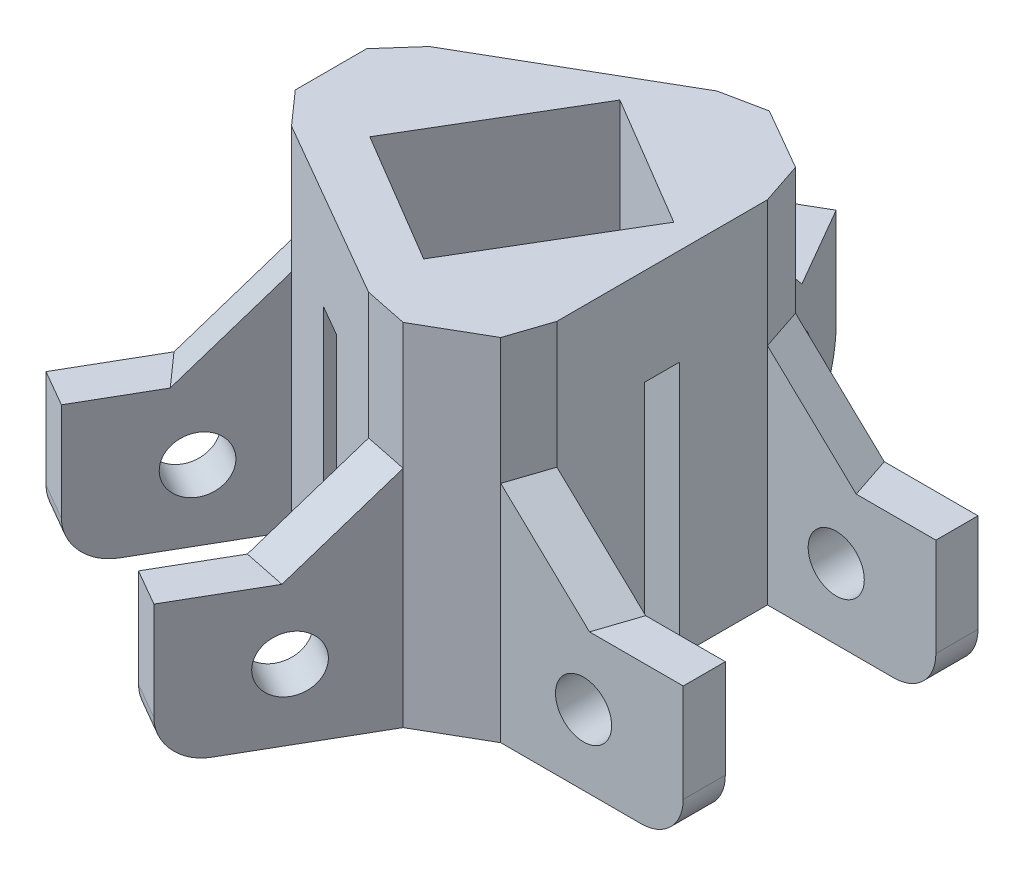
SolidWorks part; units mm, degrees
ref_plane "Front Plane" through (0, 0, 0) normal (0, 0, 1) x (1, 0, 0)
ref_plane "Top Plane" through (0, 0, 0) normal (0, 1, 0) x (1, 0, 0)
ref_plane "Right Plane" through (0, 0, 0) normal (1, 0, 0) x (0, 0, -1)
sketch "Sketch1" plane through (0, 0, 0) normal (0, 1, 0) x (1, 0, 0)
  line L13 (10, 7.5) -> (10, -7.5)
  line L24 (10, 7.5) -> (22, 7.5)
  line L62 (22, 7.5) -> (22, 10.5)
  line L64 (10, -7.5) -> (22, -7.5)
  line L66 (22, -7.5) -> (22, -10.5)
  line L67 (9, -10.5) -> (22, -10.5)
  line L68 (1.4952, -12.4103) -> (-4.5048, -22.8026)
  line L71 (-4.5048, -22.8026) -> (-1.9067, -24.3026)
  line L72 (-11.4952, -4.9103) -> (-17.4952, -15.3026)
  line L74 (-13.5933, -2.5442) -> (-20.0933, -13.8026)
  line L75 (-17.4952, -15.3026) -> (-20.0933, -13.8026)
  line L76 (-11.4952, 4.9103) -> (-17.4952, 15.3026)
  line L79 (-17.4952, 15.3026) -> (-20.0933, 13.8026)
  line L80 (1.4952, 12.4103) -> (-4.5048, 22.8026)
  line L82 (4.5933, 13.0442) -> (-1.9067, 24.3026)
  line L83 (-4.5048, 22.8026) -> (-1.9067, 24.3026)
  line L84 (1.4952, -12.4103) -> (-11.4952, -4.9103)
  line L85 (-11.4952, 4.9103) -> (1.4952, 12.4103)
  line L86 (22, 10.5) -> (9, 10.5)
  line L87 (-1.9067, -24.3026) -> (4.5933, -13.0442)
  line L88 (-20.0933, 13.8026) -> (-13.5933, 2.5442)
  line L89 (9, 10.5) -> (4.5933, 13.0442)
  line L90 (-13.5933, 2.5442) -> (-13.5933, -2.5442)
  line L91 (4.5933, -13.0442) -> (9, -10.5)
  circle A0 centre (0, 0) radius 3.5
  circle A13 centre (0, 0) radius 25 construction
  point P5 (10, 0)
  point P19 (0, 0)
  point P36 (0, 0)
  point P56 (0, 0)
  dimension "D1" = 7
  dimension "D9" = 13
  dimension "D10" = 10
  dimension "D6" = 12
  dimension "D2" = 15
  dimension "D3" = 3
  dimension "D5" = 3
  dimension "D7" = 3
  dimension "D8" = 13
  dimension "D4" = 12
extrude "Boss-Extrude1" add sketch "Sketch1" along normal mid plane 10
sketch "Sketch2" plane through (6.0622, 0, 0) normal (0, 0, 1) x (1, 0, 0)
  line L6 (-6.0622, -5) -> (-6.0622, 5) construction
  circle A0 centre (8.8378, 0) radius 3 construction
  circle A1 centre (8.8378, 0) radius 2
  dimension "D1" = 4
  dimension "D2" = 6
  dimension "D3" = 14.9
extrude "Cut-Extrude1" cut sketch "Sketch2" against normal mid plane 25 contours A1 region at (14.9, 0, 0)
sketch "Sketch5" plane through (0, 5, 0) normal (0, 1, 0) x (1, 0, 0)
  line L0 (-1.4081, 8.3975) -> (8.0486, 2.7786) construction
  line L5 (-1.4081, 8.3975) -> (8.0486, 2.7786)
  line L6 (-1.4081, 8.3975) -> (-8.0486, -2.7786)
  line L7 (8.0486, 2.7786) -> (1.4081, -8.3975)
  line L8 (-8.0486, -2.7786) -> (1.4081, -8.3975)
  line L9 (-1.4081, 8.3975) -> (1.4081, -8.3975) construction
  line L10 (-11.4952, 4.9103) -> (-13.5933, 2.5442)
  line L11 (-13.5933, -2.5442) -> (-11.4952, -4.9103)
  line L12 (1.4952, -12.4103) -> (4.5933, -13.0442)
  line L13 (9, -10.5) -> (10, -7.5)
  line L14 (10, 7.5) -> (9, 10.5)
  line L15 (4.5933, 13.0442) -> (1.4952, 12.4103)
  line L20 (22, -10.5) -> (22, -7.5)
  line L34 (-13.5933, -2.5442) -> (-20.0933, -13.8026)
  line L35 (-20.0933, -13.8026) -> (-17.4952, -15.3026)
  line L36 (-17.4952, -15.3026) -> (-11.4952, -4.9103)
  line L73 (22, -7.5) -> (10, -7.5)
  line L75 (10, -7.5) -> (10, 7.5)
  line L77 (10, -7.5) -> (10, 7.5)
  line L79 (10, 7.5) -> (22, 7.5)
  line L81 (22, 7.5) -> (22, 10.5)
  line L83 (4.5933, 13.0442) -> (-1.9067, 24.3026)
  line L85 (-1.9067, 24.3026) -> (-4.5048, 22.8026)
  line L87 (-4.5048, 22.8026) -> (1.4952, 12.4103)
  line L88 (1.4952, 12.4103) -> (-11.4952, 4.9103)
  line L89 (1.4952, 12.4103) -> (-11.4952, 4.9103)
  line L91 (-11.4952, 4.9103) -> (-17.4952, 15.3026)
  line L92 (-17.4952, 15.3026) -> (-20.0933, 13.8026)
  line L93 (-11.4952, -4.9103) -> (1.4952, -12.4103)
  line L94 (-11.4952, -4.9103) -> (1.4952, -12.4103)
  line L95 (1.4952, -12.4103) -> (-4.5048, -22.8026)
  line L97 (-4.5048, -22.8026) -> (-1.9067, -24.3026)
  line L98 (9, -10.5) -> (22, -10.5)
  line L100 (22, 10.5) -> (9, 10.5)
  line L101 (9, 10.5) -> (4.5933, 13.0442)
  line L103 (9, 10.5) -> (4.5933, 13.0442)
  line L104 (-20.0933, 13.8026) -> (-13.5933, 2.5442)
  line L105 (-13.5933, 2.5442) -> (-13.5933, -2.5442)
  line L106 (-13.5933, 2.5442) -> (-13.5933, -2.5442)
  line L107 (-1.9067, -24.3026) -> (4.5933, -13.0442)
  line L108 (4.5933, -13.0442) -> (9, -10.5)
  line L109 (4.5933, -13.0442) -> (9, -10.5)
  point P2 (0, 0)
  point P8 (0, 0)
  dimension "D2" = 11
  dimension "D3" = 13
  dimension "D1" = 0
extrude "Boss-Extrude2" add sketch "Sketch5" along normal blind 15
chamfer "Chamfer1" distance 6 angle 45 6 edges at (3.0442, 5, -12.7272) (-12.5442, 5, -3.7272) (-12.5442, 5, 3.7272) (3.0442, 5, 12.7272) (9.5, 5, 9) (9.5, 5, -9)
fillet "Fillet1" radius 3 6 edges at (-3.2058, -5, -23.5526) (22, -5, -9) (22, -5, 9) (-3.2058, -5, 23.5526) (-18.7942, -5, 14.5526) (-18.7942, -5, -14.5526)
sketch "Sketch6" plane through (0, 0, 0) normal (0, 0, 1) x (1, 0, 0)
  circle A0 centre (14.9, 0) radius 14
  dimension "D1" = 28
extrude "Cut-Extrude2" cut sketch "Sketch6" against normal mid plane 2.5
pattern_circular "CirPattern1" count 3 over 360 about axis through (0, 5, 0) along (0, 1, 0) of "Cut-Extrude1", "Cut-Extrude2"
